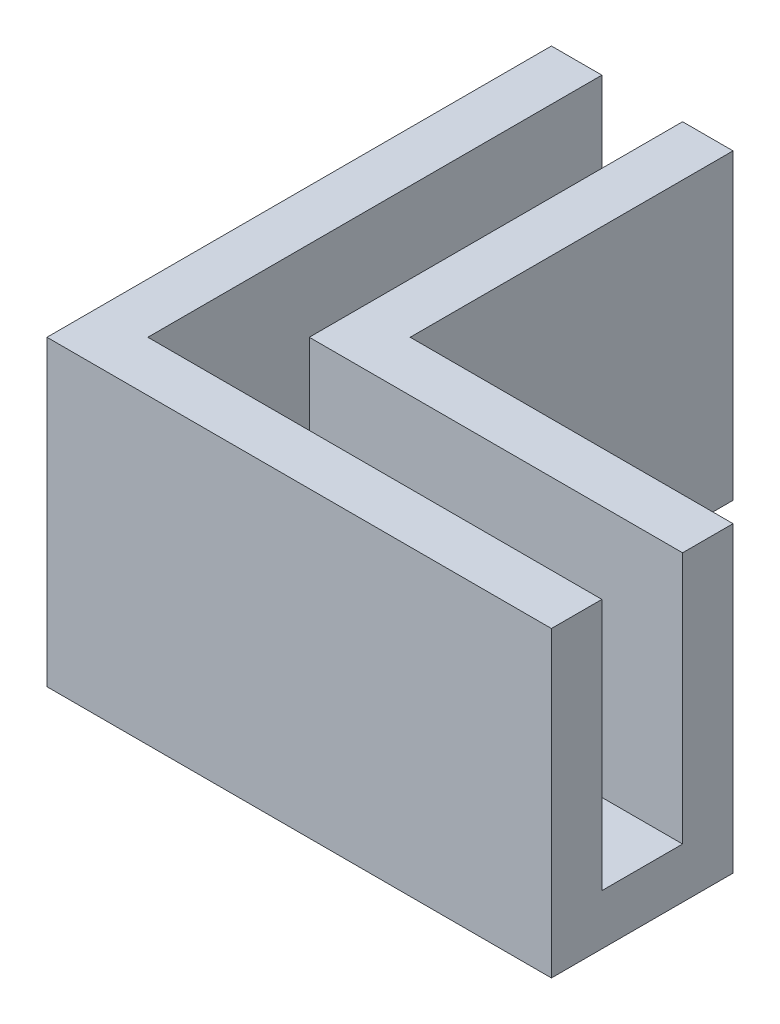
SolidWorks part; units mm, degrees
ref_plane "Front Plane" through (0, 0, 0) normal (0, 0, 1) x (1, 0, 0)
ref_plane "Top Plane" through (0, 0, 0) normal (0, 1, 0) x (1, 0, 0)
ref_plane "Right Plane" through (0, 0, 0) normal (1, 0, 0) x (0, 0, -1)
sketch "Sketch1" plane through (0, 0, 0) normal (0, 1, 0) x (1, 0, 0)
  line L0 (0, 0) -> (0, 50)
  line L1 (0, 50) -> (18, 50)
  line L2 (18, 50) -> (18, 18)
  line L3 (0, 0) -> (18, 18) construction
  line L4 (50, 18) -> (18, 18)
  line L5 (50, 0) -> (50, 18)
  line L6 (0, 0) -> (50, 0)
  line L7 (5, 5) -> (5, 50)
  line L8 (5, 50) -> (13, 50)
  line L9 (13, 50) -> (13, 13)
  line L10 (5, 5) -> (13, 13) construction
  line L11 (50, 13) -> (13, 13)
  line L12 (5, 5) -> (50, 5)
  point P9 (9, 9)
  point P12 (9, 9)
  dimension "D1" = 18
  dimension "D2" = 50
  dimension "D3" = 45
  dimension "D4" = 45
  dimension "D5" = 8
extrude "Boss-Extrude1" add sketch "Sketch1" along normal blind 5 contours L7 L12 L5 L11 L9 L1 region at (9, 0, -49.3636)
extrude "Boss-Extrude2" add sketch "Sketch1<3>" along normal blind 30 contours L12 L7 L1 L0 L6 L5 | L11 L5 L4 L2 L1 L9 region at (0.7071, 0, -25) region at (15.5, 0, -49.4767)
sketch "Sketch1<3>" plane through (0, 0, 0) normal (0, 1, 0) x (1, 0, 0) same geometry as "Sketch1"
